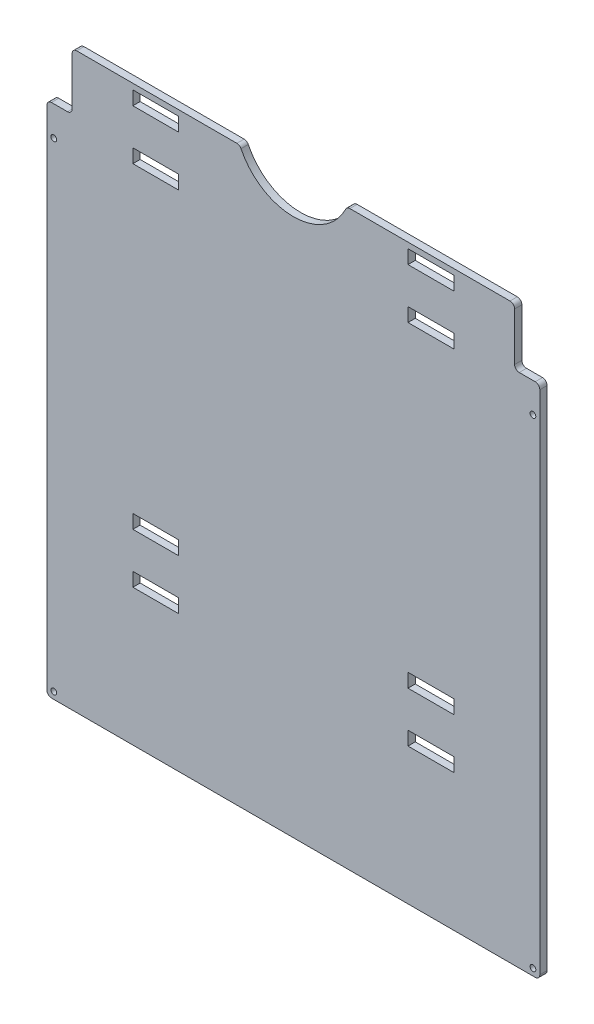
SolidWorks part; units mm, degrees
ref_plane "Front Plane" through (0, 0, 0) normal (0, 0, 1) x (1, 0, 0)
ref_plane "Top Plane" through (0, 0, 0) normal (0, 1, 0) x (1, 0, 0)
ref_plane "Right Plane" through (0, 0, 0) normal (1, 0, 0) x (0, 0, -1)
sketch "Sketch1" plane through (0, 0, 0) normal (0, 0, 1) x (1, 0, 0)
  line L1 (-107.5, -125) -> (107.5, -125)
  line L2 (-107.5, -125) -> (-107.5, 125)
  line L3 (-107.5, 125) -> (107.5, 125)
  line L4 (107.5, -125) -> (107.5, 125)
  line L5 (-107.5, -125) -> (107.5, 125) construction
  line L6 (-107.5, 125) -> (107.5, -125) construction
  point P0 (0, 0)
  dimension "D1" = 215
  dimension "D2" = 250
extrude "Boss-Extrude1" add sketch "Sketch1" along normal blind 3.175
sketch "Sketch2" plane through (0, 0, 3.175) normal (0, 0, 1) x (1, 0, 0)
  line L0 (107.5, -125) -> (107.5, 125) construction
  line L1 (107.5, 125) -> (-107.5, 125) construction
  circle A0 centre (0, 135) radius 25.4
  dimension "D3" = 50.8
  dimension "D1" = 107.5
  dimension "D2" = 10
extrude "Cut-Extrude1" cut sketch "Sketch2" against normal through all
sketch "Sketch3" plane through (0, 0, 3.175) normal (0, 0, 1) x (1, 0, 0)
  line L1 (-107.5, 125) -> (-96.5, 125)
  line L2 (-107.5, 125) -> (-107.5, 100)
  line L3 (-107.5, 100) -> (-96.5, 100)
  line L4 (-96.5, 125) -> (-96.5, 100)
  dimension "D1" = 11
  dimension "D2" = 25
extrude "Cut-Extrude2" cut sketch "Sketch3" against normal through all
mirror "Mirror1" about plane through (0, 0, 0) normal (1, 0, 0) of "Cut-Extrude2"
fillet "Fillet1" radius 2 10 edges at (107.5, 100, 1.5875) (107.5, -125, 1.5875) (-107.5, -125, 1.5875) (-107.5, 100, 1.5875) (-96.5, 100, 1.5875) (23.3487, 125, 1.5875) (96.5, 125, 1.5875) (96.5, 100, 1.5875) (-23.3487, 125, 1.5875) (-96.5, 125, 1.5875)
sketch "Sketch4" plane through (0, 0, 0) normal (0, 0, -1) x (-1, 0, 0)
  line L1 (-70, -43.5) -> (-50, -43.5)
  line L2 (-70, -43.5) -> (-70, -37.5)
  line L3 (-70, -37.5) -> (-50, -37.5)
  line L4 (-50, -43.5) -> (-50, -37.5)
  line L5 (-70, -59.375) -> (-50, -59.375)
  line L6 (-70, -59.375) -> (-70, -65.375)
  line L7 (-70, -65.375) -> (-50, -65.375)
  line L8 (-50, -59.375) -> (-50, -65.375)
  dimension "D1" = 6
  dimension "D2" = 15.875
  dimension "D3" = 43.5
  dimension "D4" = 50
  dimension "D5" = 20
extrude "Cut-Extrude3" cut sketch "Sketch4" against normal through all
mirror "Mirror2" about plane through (0, 0, 0) normal (1, 0, 0) of "Cut-Extrude3"
pattern_linear "LPattern1" count 2 spacing 160 along (0, 1, 0) of "Cut-Extrude3", "Mirror2"
sketch "Sketch5" plane through (0, 0, 3.175) normal (0, 0, 1) x (1, 0, 0)
  line L0 (-105.5, -125) -> (105.5, -125) construction
  line L1 (-104.5, -122) -> (104.5, -122) construction
  line L2 (-104.5, -122) -> (-104.5, 87) construction
  line L3 (-104.5, 87) -> (104.5, 87) construction
  line L4 (104.5, -122) -> (104.5, 87) construction
  line L5 (-107.5, 98) -> (-107.5, -123) construction
  circle A0 centre (-104.5, 87) radius 1.5
  circle A1 centre (104.5, 87) radius 1.5
  circle A2 centre (104.5, -122) radius 1.5
  circle A3 centre (-104.5, -122) radius 1.5
  dimension "D5" = 3
  dimension "D1" = 3
  dimension "D2" = 3
  dimension "D3" = 209
  dimension "D4" = 209
hole_wizard "M3x0.5 Tapped Hole1" positions "Sketch7" profile "Sketch8" tap size "M3x0.5" standard "ANSI Metric" end condition through all
sketch "Sketch7" plane through (0, 0, 0) normal (0, 0, -1) x (-1, 0, 0)
  point P0 (-104.5, 87)
  point P3 (104.5, 87)
  point P6 (104.5, -122)
  point P9 (-104.5, -122)
sketch "Sketch8" plane through (104.5, 87, 0) normal (1, 0, 0) x (0, 1, 0)
  line L0 (0, 0) -> (0, 3.175)
  line L1 (0, 3.175) -> (1.25, 3.175)
  line L2 (1.25, 3.175) -> (1.25, 0)
  line L5 (1.25, 0) -> (0, 0)
  line L11 (0, -6.35) -> (0, 107.95) construction
  dimension "Thread Major Dia." = 2.5
  dimension "Thru Tap Drill Depth" = 3.175
